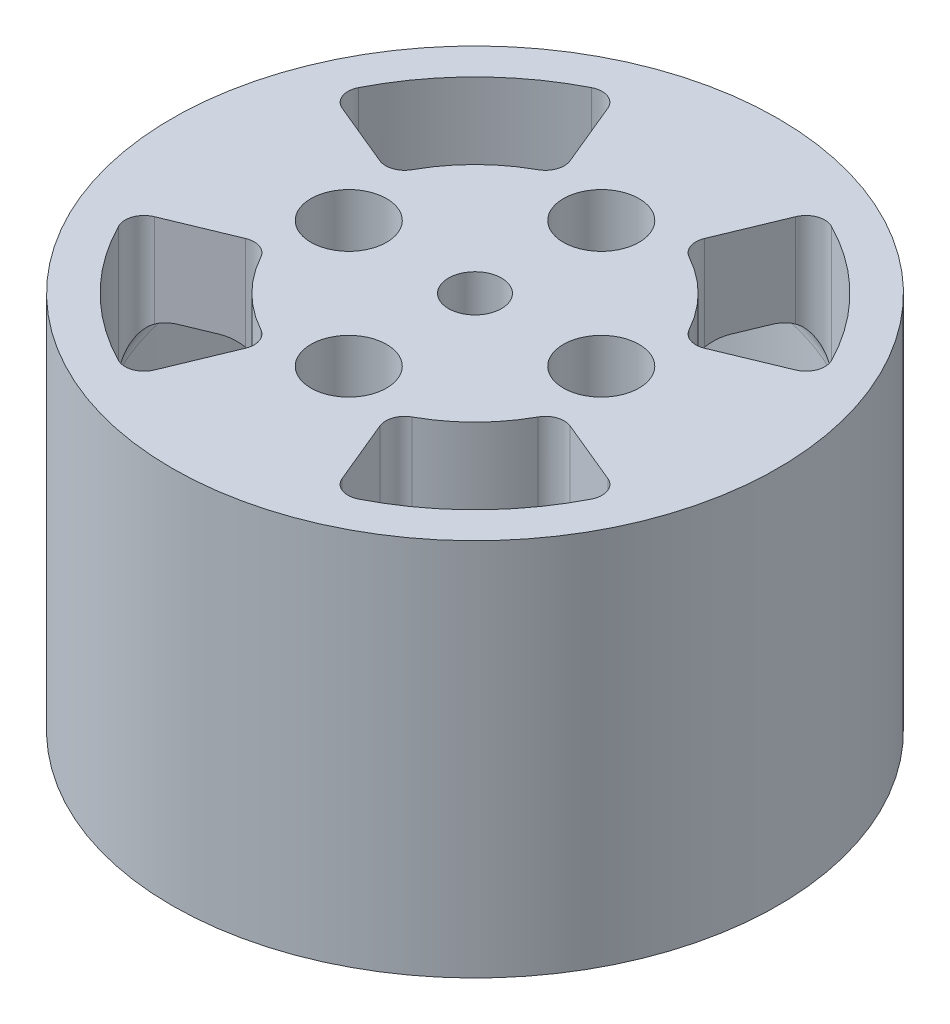
SolidWorks part; units mm, degrees
ref_plane "前视基准面" through (0, 0, 0) normal (0, 0, 1) x (1, 0, 0)
ref_plane "上视基准面" through (0, 0, 0) normal (0, 1, 0) x (1, 0, 0)
ref_plane "右视基准面" through (0, 0, 0) normal (1, 0, 0) x (0, 0, -1)
sketch "草图1" plane through (0, 0, 0) normal (0, 1, 0) x (1, 0, 0)
  circle A0 centre (0, 0) radius 24
  dimension "D1" = 48
extrude "凸台-拉伸1" add sketch "草图1" along normal blind 30
sketch "草图2" plane through (0, 0, 0) normal (0, -1, 0) x (1, 0, 0)
  circle A0 centre (0, 0) radius 21
  dimension "D1" = 42
extrude "切除-拉伸1" cut sketch "草图2" against normal blind 20
sketch "草图3" plane through (0, 30, 0) normal (0, 1, 0) x (1, 0, 0)
  circle A0 centre (0, 0) radius 10 construction
  circle A1 centre (0, 10) radius 1.65
  circle A2 centre (10, 0) radius 1.65
  circle A3 centre (0, -10) radius 1.65
  circle A4 centre (-10, 0) radius 1.65
  dimension "D1" = 20
  dimension "D2" = 3.3
extrude "切除-拉伸2" cut sketch "草图3" against normal up to next
sketch "草图4" plane through (0, 30, 0) normal (0, 1, 0) x (1, 0, 0)
  circle A0 centre (0, 10) radius 3
  circle A1 centre (10, 0) radius 3
  circle A2 centre (0, -10) radius 3
  circle A3 centre (-10, 0) radius 3
  dimension "D1" = 6
extrude "切除-拉伸3" cut sketch "草图4" against normal blind 5
sketch "草图5" plane through (0, 30, 0) normal (0, 1, 0) x (1, 0, 0)
  circle A0 centre (0, 0) radius 2.1
  dimension "D1" = 4.2
extrude "切除-拉伸4" cut sketch "草图5" against normal up to next
sketch "草图6" plane through (0, 20, 0) normal (0, -1, 0) x (1, 0, 0)
  line L0 (0, 0) -> (-4.7835, 11.5485) construction
  line L1 (-4.7835, 11.5485) -> (-8.0364, 19.4015)
  line L2 (0, 0) -> (-11.5485, 4.7835) construction
  line L3 (-11.5485, 4.7835) -> (-19.4015, 8.0364)
  line L4 (0, 0) -> (-12.5, 0) construction
  line L5 (0, 0) -> (0, 12.5) construction
  circle A0 centre (0, 0) radius 21 construction
  circle A1 centre (0, 0) radius 21 construction
  circle A2 centre (0, 0) radius 12.5 construction
  arc A3 (-19.4015, 8.0364) -> (-8.0364, 19.4015) centre (0, 0) cw
  arc A4 (-11.5485, 4.7835) -> (-4.7835, 11.5485) centre (0, 0) cw
  dimension "D1" = 25
  dimension "D2" = 22.5
  dimension "D3" = 22.5
extrude "切除-拉伸5" cut sketch "草图6" against normal up to next
sketch "草图7" plane through (0, 0, 0) normal (0, 0, 1) x (1, 0, 0)
  line L0 (0, 0) -> (0, 30) construction
  line L1 (3, 30) -> (-3, 30) construction
pattern_circular "阵列(圆周)1" count 4 over 360 about axis through (0, 0, 0) along (0, 1, 0) of "切除-拉伸5"
sketch "草图8" plane through (0, 20, 0) normal (0, -1, 0) x (1, 0, 0)
  circle A1 centre (0, 0) radius 12.5
  circle A2 centre (0, 0) radius 21
extrude "切除-拉伸6" cut sketch "草图8" against normal blind 3
fillet "圆角1" radius 3 8 edges at (0, 23, -21) (0, 23, -12.5) (12.5, 23, 0) (21, 23, 0) (-12.5, 23, 0) (-21, 23, 0) (0, 23, 12.5) (0, 23, 21)
fillet "圆角2" radius 1.5 16 edges at (-4.7835, 25, 11.5485) (-11.5485, 25, 4.7835) (-19.4015, 25, 8.0364) (-8.0364, 25, 19.4015) (-11.5485, 25, -4.7835) (-4.7835, 25, -11.5485) (-8.0364, 25, -19.4015) (-19.4015, 25, -8.0364) (4.7835, 25, -11.5485) (11.5485, 25, -4.7835) (19.4015, 25, -8.0364) (8.0364, 25, -19.4015) (11.5485, 25, 4.7835) (4.7835, 25, 11.5485) (8.0364, 25, 19.4015) (19.4015, 25, 8.0364)
